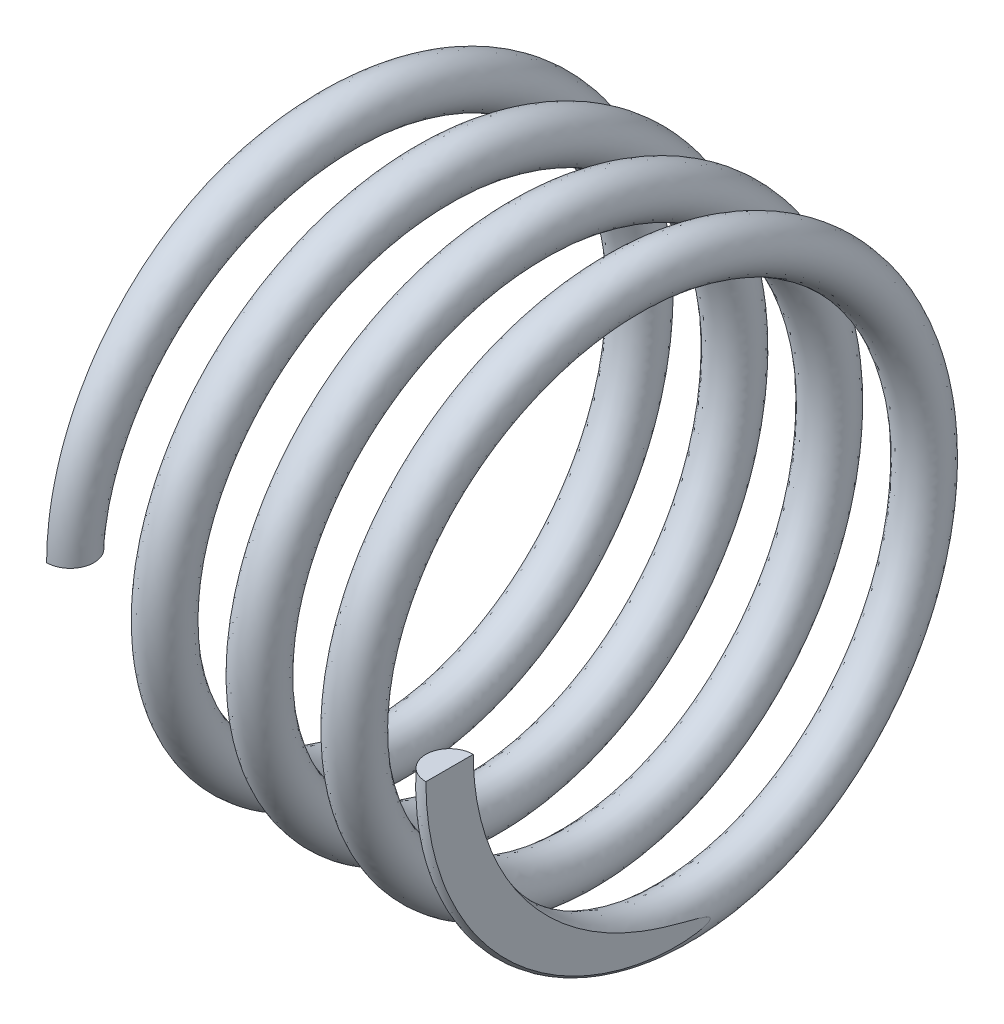
SolidWorks part; units mm, degrees
ref_plane "Спереди" through (0, 0, 0) normal (0, 0, 1) x (1, 0, 0)
ref_plane "Сверху" through (0, 0, 0) normal (0, 1, 0) x (1, 0, 0)
ref_plane "Справа" through (0, 0, 0) normal (1, 0, 0) x (0, 0, -1)
sketch "Эскиз2" plane through (0, 0, 0) normal (1, 0, 0) x (0, 0, -1)
  circle A0 centre (0, 0) radius 5.5
curve "Спираль1" pitch 2 height 8 radius 5.5 left hand yes centre (0, 0, 0) axis (1, 0, 0) start towards (0, 0, 1)
sketch "Эскиз3" plane through (0, 0, 0) normal (0, 1, 0) x (1, 0, 0)
  circle A0 centre (8.0017, -5.4991) radius 0.5
sweep "По траектории1" add profiles "Эскиз3" path "Спираль1"
sketch "Эскиз6" plane through (0, 0, 0) normal (0, 1, 0) x (1, 0, 0)
  line L1 (0.0017, -6.3636) -> (-2.2511, -6.3636)
  line L2 (0.0017, -6.3636) -> (0.0017, 0)
  line L3 (0.0017, 0) -> (-2.2511, 0)
  line L4 (-2.2511, -6.3636) -> (-2.2511, 0)
extrude "Вытянуть2" cut sketch "Эскиз6" along normal blind 10
sketch "Эскиз8" plane through (0, 0, 0) normal (0, 1, 0) x (1, 0, 0)
  line L1 (8.0017, -5.9991) -> (10.0599, -5.9991)
  line L2 (8.0017, -5.9991) -> (8.0017, 3.0518)
  line L3 (8.0017, 3.0518) -> (10.0599, 3.0518)
  line L4 (10.0599, -5.9991) -> (10.0599, 3.0518)
  circle A0 centre (8.0017, -5.4991) radius 0.5 construction
extrude "Вытянуть3" cut sketch "Эскиз8" against normal blind 10
sketch "Эскиз9" plane through (0, 0, 0) normal (1, 0, 0) x (0, 0, -1)
  circle A0 centre (0, 0) radius 8.7267
